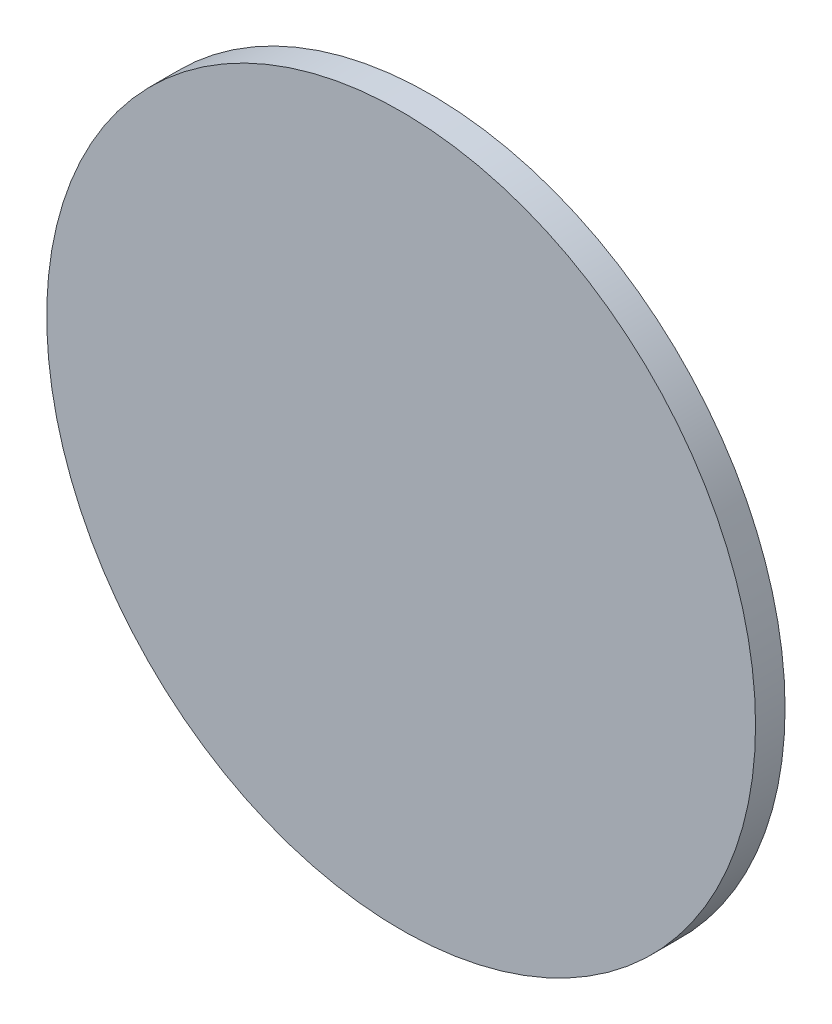
SolidWorks part; units mm, degrees
ref_plane "Front Plane" through (0, 0, 0) normal (0, 0, 1) x (1, 0, 0)
ref_plane "Top Plane" through (0, 0, 0) normal (0, 1, 0) x (1, 0, 0)
ref_plane "Right Plane" through (0, 0, 0) normal (1, 0, 0) x (0, 0, -1)
sketch "Sketch1" plane through (0, 0, 0) normal (0, 0, 1) x (1, 0, 0)
  circle A1 centre (0, 0) radius 18
  circle A2 centre (0, 0) radius 7.5
  dimension "D1" = 15
  dimension "D2" = 36
extrude "Boss-Extrude1" add sketch "Sketch1" along normal blind 1.5 contours A2 | A1 A2 region at (-17.4909, 0, 0) region at (0, 0, 0)
ref_plane "Plane1" through (0, 0, -10) normal (0, 0, -1) x (-1, 0, 0)
sketch "Sketch2" plane through (0, 0, -10) normal (0, 0, -1) x (-1, 0, 0)
  circle A0 centre (0, 0) radius 2.75
  circle A2 centre (0, 0) radius 3.25
  dimension "D1" = 5.5
  dimension "D3" = 6.5
loft "Loft1" add section "Sketch1<3>" section "Sketch2" connector at (7.3255, -1.6085, 0) connector at (2.6051, -1.9432, -10)
sketch "Sketch1<3>" plane through (0, 0, 0) normal (0, 0, 1) x (1, 0, 0) same geometry as "Sketch1"
extrude "Cut-Extrude1" cut sketch "Sketch2<3>" against normal blind 10 contours A0 region at (0, 0, -10)
sketch "Sketch2<3>" plane through (0, 0, -10) normal (0, 0, -1) x (-1, 0, 0) same geometry as "Sketch2"
